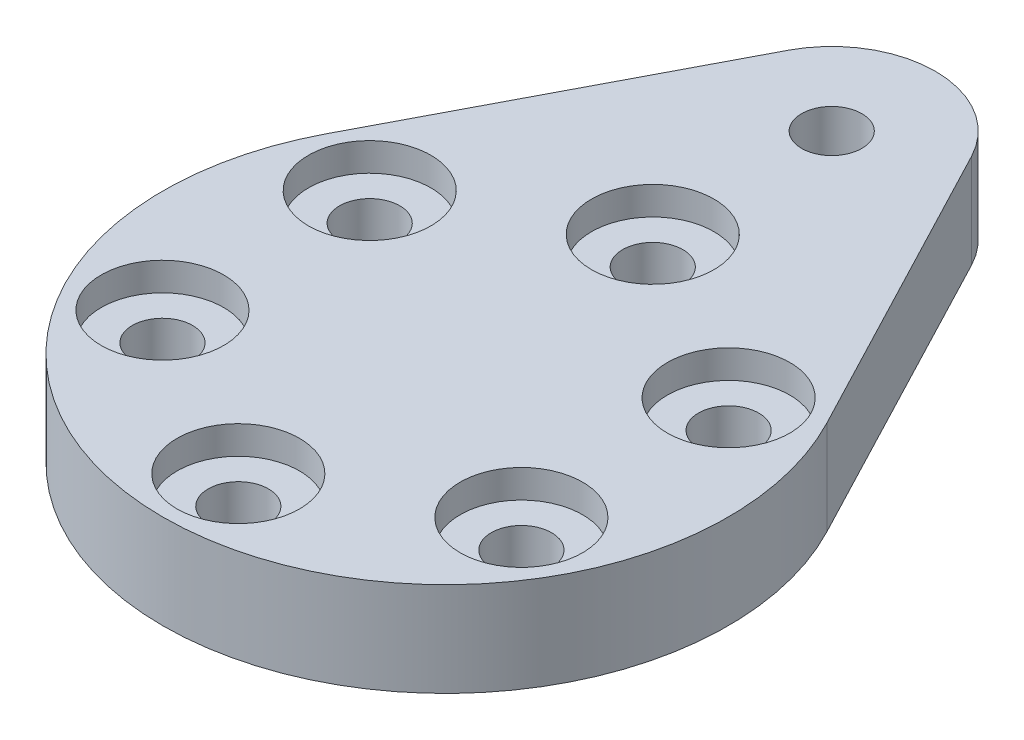
SolidWorks part; units mm, degrees
ref_plane "Front Plane" through (0, 0, 0) normal (0, 0, 1) x (1, 0, 0)
ref_plane "Top Plane" through (0, 0, 0) normal (0, 1, 0) x (1, 0, 0)
ref_plane "Right Plane" through (0, 0, 0) normal (1, 0, 0) x (0, 0, -1)
sketch "Sketch4" plane through (0, 0, 0) normal (0, 1, 0) x (1, 0, 0)
  line L0 (0, 0) -> (0, 20.5) construction
  line L1 (-4.8738, 23.0488) -> (-13.2921, 6.9512)
  line L2 (4.8738, 23.0488) -> (13.2921, 6.9512)
  circle A0 centre (0, 0) radius 11 construction
  circle A1 centre (0, 0) radius 15
  circle A2 centre (0, 11) radius 1.6
  circle A3 centre (9.5263, 5.5) radius 1.6
  circle A4 centre (9.5263, -5.5) radius 1.6
  circle A5 centre (0, -11) radius 1.6
  circle A6 centre (-9.5263, -5.5) radius 1.6
  circle A7 centre (-9.5263, 5.5) radius 1.6
  circle A8 centre (0, 20.5) radius 1.6
  circle A9 centre (0, 20.5) radius 5.5
  point P18 (0, 0)
  dimension "D1" = 22
  dimension "D2" = 30
  dimension "D3" = 3.2
  dimension "D6" = 3.2
  dimension "D5" = 20.5
  dimension "D4" = 6
extrude "Boss-Extrude1" add sketch "Sketch4" along normal blind 5 contours A9 A8 | A9 L1 A1 | A9 A1 L2 | A1 A7 A6 A5 A4 A3 A2 region at (-6.7798, 0, -15.4196) region at (0, 0, -25.8444) region at (0, 0, 0) region at (6.7798, 0, -15.4196)
sketch "Sketch6" plane through (0, 5, 0) normal (0, 1, 0) x (1, 0, 0)
  circle A0 centre (0, 0) radius 11 construction
  circle A1 centre (0, 11) radius 3.25
  circle A2 centre (9.5263, 5.5) radius 3.25
  circle A3 centre (9.5263, -5.5) radius 3.25
  circle A4 centre (0, -11) radius 3.25
  circle A5 centre (-9.5263, -5.5) radius 3.25
  circle A6 centre (-9.5263, 5.5) radius 3.25
  point P19 (0, 0)
  dimension "D1" = 6.5
  dimension "D3" = 22
  dimension "D2" = 6
extrude "Cut-Extrude1" cut sketch "Sketch6" against normal blind 1.5
